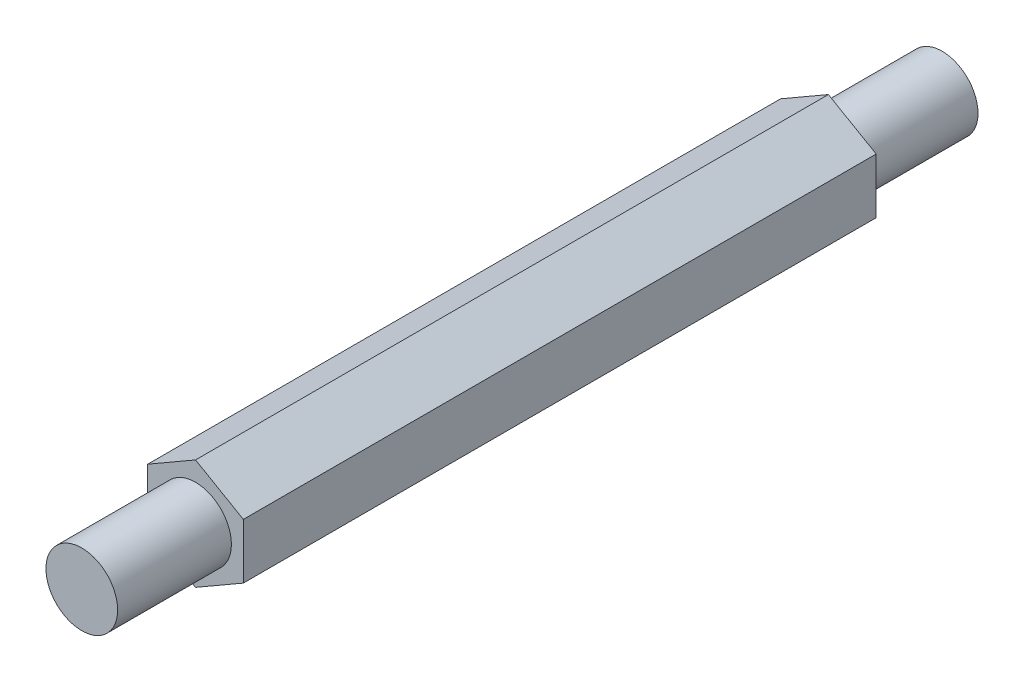
SolidWorks part; units mm, degrees
ref_plane "Front Plane" through (0, 0, 0) normal (0, 0, 1) x (1, 0, 0)
ref_plane "Top Plane" through (0, 0, 0) normal (0, 1, 0) x (1, 0, 0)
ref_plane "Right Plane" through (0, 0, 0) normal (1, 0, 0) x (0, 0, -1)
sketch "Sketch1" plane through (0, 0, 0) normal (0, 0, 1) x (1, 0, 0)
  line L1 (0, -14.6647) -> (12.7, -7.3323)
  line L2 (12.7, -7.3323) -> (12.7, 7.3323)
  line L3 (12.7, 7.3323) -> (0, 14.6647)
  line L4 (0, 14.6647) -> (-12.7, 7.3323)
  line L5 (-12.7, 7.3323) -> (-12.7, -7.3323)
  line L6 (-12.7, -7.3323) -> (0, -14.6647)
  circle A0 centre (0, 0) radius 12.7 construction
  circle A1 centre (0, 0) radius 9.525
  dimension "D2" = 19.05
  dimension "D1" = 25.4
extrude "Boss-Extrude1" add sketch "Sketch1" along normal mid plane 168.148 contours A1 | L5 L6 L1 L2 L3 L4 A1 region at (-6.156, -10.6625, 0) region at (0, 0, 0)
extrude "Boss-Extrude2" add sketch "Sketch1<3>" along normal mid plane 228.6 contours A1 region at (0, 0, 0)
sketch "Sketch1<3>" plane through (0, 0, 0) normal (0, 0, 1) x (1, 0, 0) same geometry as "Sketch1"
